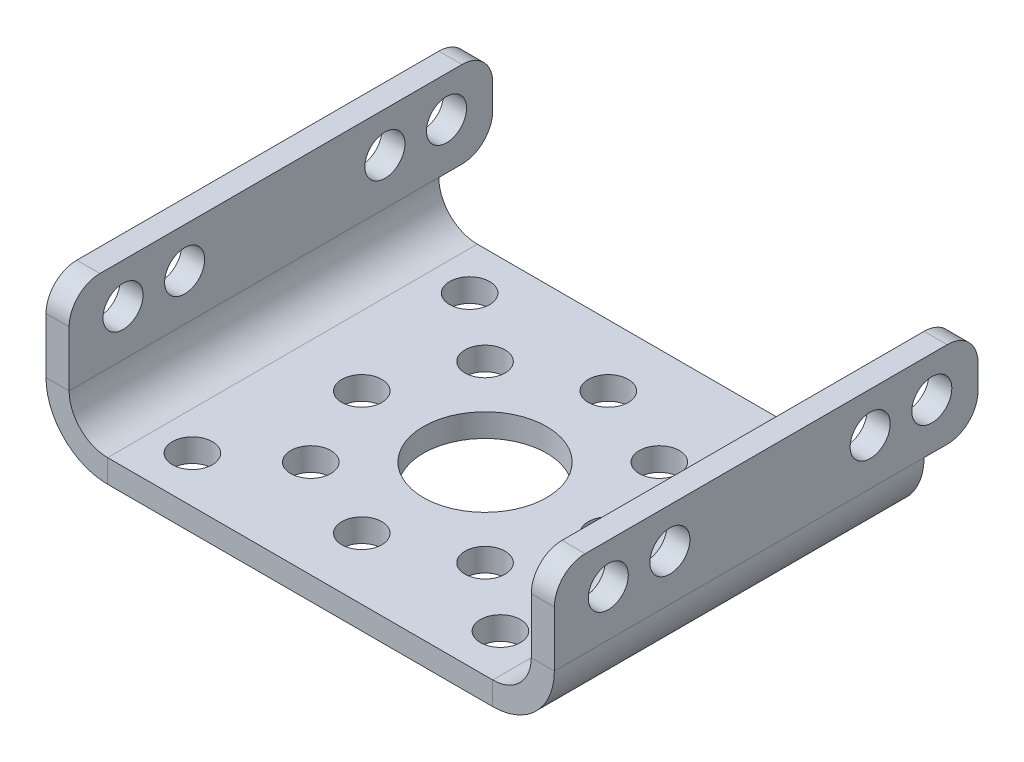
SolidWorks part; units mm, degrees
note: The reader was unsure of these and kept them because the rebuilt part matched: bend radius of "Base-Flange1", "BaseBend1", "BaseBend2".
material "2024 Alloy (SN)"
ref_plane "Front Plane" through (0, 0, 0) normal (0, 0, 1) x (1, 0, 0)
ref_plane "Top Plane" through (0, 0, 0) normal (0, 1, 0) x (1, 0, 0)
ref_plane "Right Plane" through (0, 0, 0) normal (1, 0, 0) x (0, 0, -1)
sketch "Sketch1" plane through (0, 0, 0) normal (0, 0, 1) x (1, 0, 0)
  line L0 (-15, 8.1) -> (-15, 0)
  line L1 (-15, 0) -> (15, 0)
  line L2 (15, 0) -> (15, 8.1)
  point P2 (0, 0)
  dimension "D1" = 8.1
  dimension "D2" = 30
sheet metal parameters "Sheet-Metal1" thickness 1.5 parameters "D1"=2.5
base flange "Base-Flange1" sketch "Sketch1" end condition mid plane depth 24 reverse direction no thickness 1.5 reverse thickness direction no bend radius 2.5
bend "BaseBend1" bend radius 2.5 bend angle 90 parameters "D5"=1
bend "BaseBend2" bend radius 2.5 bend angle 90 parameters "D5"=2
sketch "Sketch5" plane through (0, 0, 0) normal (0, 1, 0) x (1, 0, 0)
  circle A0 centre (0, 0) radius 4
  circle A1 centre (0, 8) radius 1.3
  circle A2 centre (5.6569, 5.6569) radius 1.3
  circle A3 centre (8, 0) radius 1.3
  circle A4 centre (5.6569, -5.6569) radius 1.3
  circle A5 centre (0, -8) radius 1.3
  circle A6 centre (-5.6569, -5.6569) radius 1.3
  circle A7 centre (-8, 0) radius 1.3
  circle A8 centre (-5.6569, 5.6569) radius 1.3
  dimension "D1" = 8
  dimension "D2" = 2.6
  dimension "D3" = 8
  dimension "D4" = 8
extrude "Cut-Extrude1" cut sketch "Sketch5" against normal blind 10 normal cut yes
sketch "Sketch6" plane through (0, 0, -12) normal (0, 0, -1) x (-1, 0, 0)
  line L0 (15, 8.1) -> (15, 2.5) construction
  line L1 (16.5, 8.1) -> (16.5, 2.5) construction
  line L2 (16.5, 8.1) -> (15, 8.1) construction
  line L3 (15, 2.5) -> (16.5, 2.5) construction
  line L4 (-16.5, 8.1) -> (-16.5, 2.5)
  line L5 (-16.5, 2.5) -> (-15, 2.5)
  line L6 (-15, 2.5) -> (-15, 8.1)
  line L7 (-15, 8.1) -> (-16.5, 8.1)
  line L8 (-16.5, 8.1) -> (-16.5, 2.5)
  line L9 (-16.5, 2.5) -> (-15, 2.5)
  line L10 (-15, 2.5) -> (-15, 8.1)
  line L11 (-15, 8.1) -> (-16.5, 8.1)
  line L12 (15, 8.1) -> (15, 2.5)
  line L13 (16.5, 8.1) -> (16.5, 2.5)
  line L14 (16.5, 8.1) -> (15, 8.1)
  line L15 (15, 2.5) -> (16.5, 2.5)
  dimension "D1" = 0
extrude "Boss-Extrude1" add sketch "Sketch6" along normal blind 3.5
sketch "Sketch7" plane through (0, 0, 0) normal (1, 0, 0) x (0, 0, -1)
  line L0 (-12, 0) -> (12, 0) construction
  circle A0 centre (-8.5, 5.5) radius 1.3
  circle A1 centre (-4.5, 5.5) radius 1.3
  circle A2 centre (8.5, 5.5) radius 1.3
  circle A3 centre (12.5, 5.5) radius 1.3
  dimension "D1" = 5.5
  dimension "D2" = 8.5
  dimension "D3" = 17
  dimension "D4" = 17
  dimension "D5" = 4
  dimension "D6" = 2.6
extrude "Cut-Extrude2" cut sketch "Sketch7" against normal through all and the other way through all normal cut yes
fillet "Fillet1" radius 2 6 edges at (-15.75, 8.1, 12) (15.75, 8.1, 12) (-15.75, 2.5, -15.5) (-15.75, 8.1, -15.5) (15.75, 8.1, -15.5) (15.75, 2.5, -15.5)
sketch "Sketch8" plane through (0, 0, 0) normal (0, 1, 0) x (1, 0, 0)
  circle A0 centre (-10, 9) radius 1.3
  circle A1 centre (10, 9) radius 1.3
  circle A2 centre (-10, -9) radius 1.3
  circle A3 centre (10, -9) radius 1.3
  dimension "D1" = 10
  dimension "D4" = 9
  dimension "D5" = 2.6
  dimension "D2" = 10
  dimension "D3" = 9
extrude "Cut-Extrude3" cut sketch "Sketch8" against normal blind 10 normal cut yes
flat pattern "Flat-Pattern1" [suppressed]
sketch "Bend-Lines1" plane through (0, 0, 0) normal (0, 1, 0) x (-1, 0, 0)
  line L0 (16.0525, 12) -> (16.0525, -12) construction
  line L1 (-16.0525, -12) -> (-16.0525, 12) construction
  line L2 (16.0525, 12) -> (16.0525, -12) construction
  line L3 (-16.0525, -12) -> (-16.0525, 12) construction
sketch3d "Bounding-Box1" [suppressed]
  line L0 (8.2051, 0, 0) -> (-40.2051, 0, 0) construction
  line L1 (8.2051, -27.5, 0) -> (-40.2051, -27.5, 0) construction
  line L2 (8.2051, 0, 0) -> (8.2051, -27.5, 0) construction
  line L3 (-40.2051, 0, 0) -> (-40.2051, -27.5, 0) construction
bend of the flat pattern "Flatten-<BaseBend1>1"
bend of the flat pattern "Flatten-<BaseBend2>1"
